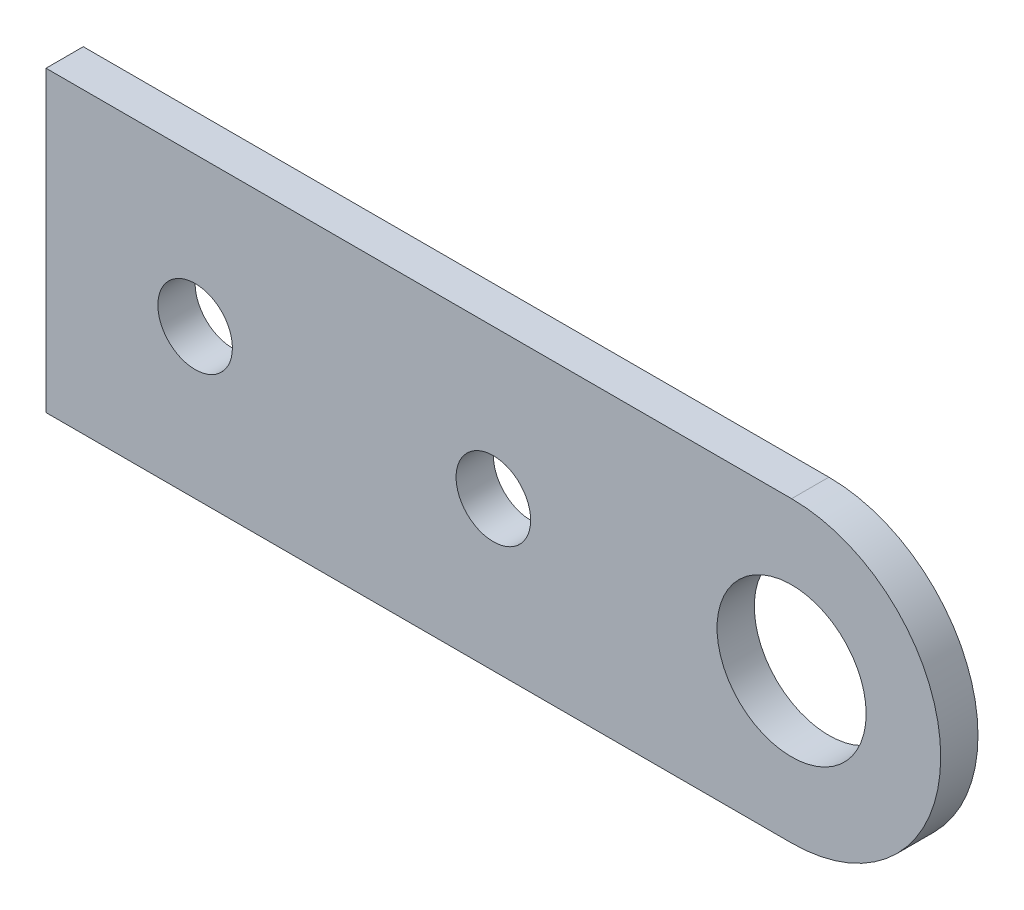
SolidWorks part; units mm, degrees
material "6061-T6 (SS)"
ref_plane "Front Plane" through (0, 0, 0) normal (0, 0, 1) x (1, 0, 0)
ref_plane "Top Plane" through (0, 0, 0) normal (0, 1, 0) x (1, 0, 0)
ref_plane "Right Plane" through (0, 0, 0) normal (1, 0, 0) x (0, 0, -1)
sketch "Sketch1" plane through (0, 0, 0) normal (0, 0, 1) x (1, 0, 0)
  line L0 (12.7, 0) -> (-12.7, 0) construction
  line L1 (0, 12.7) -> (-63.5, 12.7)
  line L2 (0, 12.7) -> (0, -12.7) construction
  line L3 (0, -12.7) -> (-63.5, -12.7)
  line L4 (-63.5, 12.7) -> (-63.5, -12.7)
  circle A0 centre (0, 0) radius 6.35
  arc A1 (0, 12.7) -> (0, -12.7) centre (0, 0) cw
  circle A2 centre (-50.8, 0) radius 3.175
  circle A3 centre (-25.4, 0) radius 3.175
  point P13 (0, 0)
  dimension "D3" = 12.7
  dimension "D4" = 6.35
  dimension "D1" = 25.4
  dimension "D2" = 50.8
  dimension "D5" = 12.7
  dimension "D6" = 25.4
base flange "Base-Flange1" sketch "Sketch1" thickness 3.175 reverse thickness direction no parameters "D1"=0.7366
sketch "Bend-Lines1" [suppressed] plane through (0, 0, 0) normal (0, 1, 0) x (1, 0, 0)
sketch "Bounding-Box1" [suppressed] plane through (0, 0, 0) normal (0, 1, 0) x (1, 0, 0)
sheet metal parameters "Sheet-Metal1" thickness 3.175 parameters "D1"=0.7366
flat pattern "Flat-Pattern1" [suppressed]
sketch "Bend-Lines2" plane through (0, 0, 0) normal (0, 1, 0) x (1, 0, 0)
sketch3d "Bounding-Box2" [suppressed]
  line L0 (-63.5, 12.7, 0) -> (12.6999, 12.7, 0) construction
  line L1 (-63.5, -12.7, 0) -> (12.6999, -12.7, 0) construction
  line L2 (-63.5, 12.7, 0) -> (-63.5, -12.7, 0) construction
  line L3 (12.6999, 12.7, 0) -> (12.6999, -12.7, 0) construction
